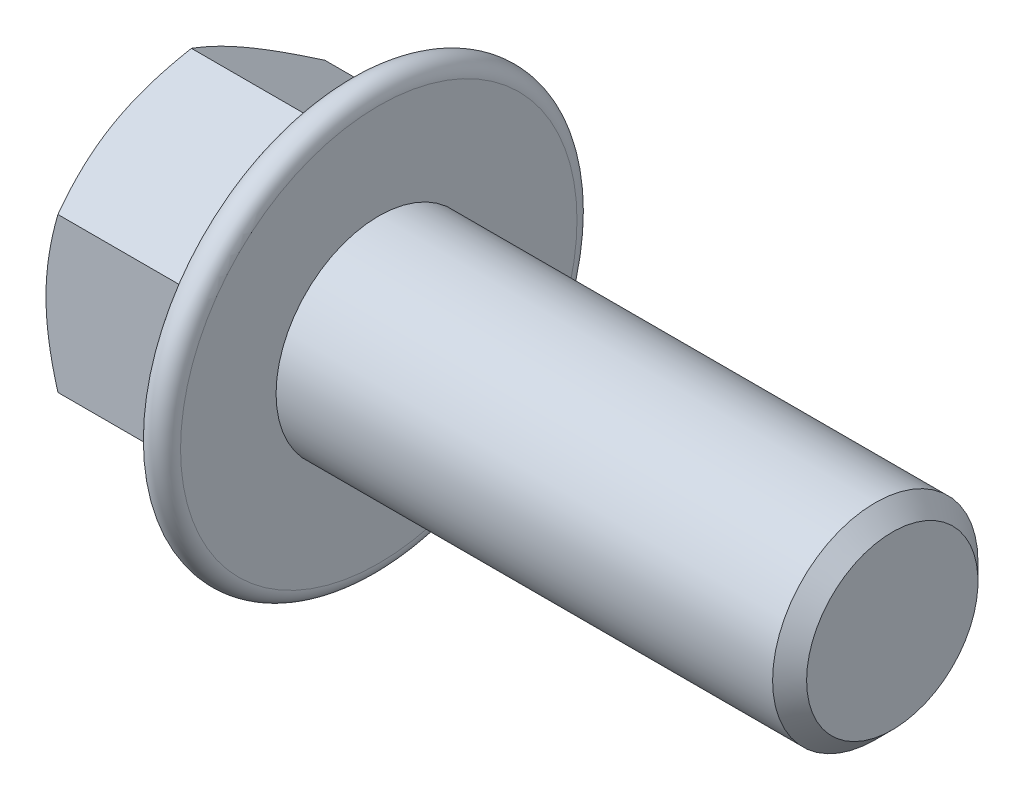
SolidWorks part; units mm, degrees
extrude "BaseHead" add sketch "Sketch1" along normal blind 9.7
sketch "Sketch1" plane through (0, 0, 0) normal (1, 0, 0) x (0, 0, -1)
  line L0 (6.5, 3.7528) -> (6.5, -3.7528)
  line L1 (-6.5, 3.7528) -> (-6.5, -3.7528)
  line L2 (6.5, -3.7528) -> (0, -7.5056)
  line L3 (0, -7.5056) -> (-6.5, -3.7528)
  line L4 (6.5, 3.7528) -> (0, 7.5056)
  line L5 (0, 7.5056) -> (-6.5, 3.7528)
  dimension "D2" = 120
  dimension "D3" = 6.5
  dimension "D4" = 6.5
  dimension "D5" = 6.5
ref_plane "Plane1" through (0, 0, 0) normal (0, 0, 1) x (1, 0, 0)
ref_plane "Plane2" through (0, 0, 0) normal (0, 1, 0) x (1, 0, 0)
ref_plane "Plane3" through (0, 0, 0) normal (1, 0, 0) x (0, 0, -1)
sketch "BodySke" plane through (0, 0, 0) normal (0, 0, 1) x (1, 0, 0)
  line L0 (0, 3.7528) -> (0, -3.7528) construction
  line L1 (0, 0) -> (34.7, 0)
  line L2 (0, 0) -> (0, 5)
  line L3 (0, 5) -> (33.872, 5)
  line L4 (34.7, 0) -> (34.7, 4.172)
  line L5 (9.7, 7.5056) -> (9.7, 3.7528) construction
  line L6 (34.7, 4.172) -> (33.872, 5)
  line L7 (0, 0) -> (96.52, 0) construction
  line L8 (34.7, -4.172) -> (33.872, -5) construction
  line L9 (0, -5) -> (33.872, -5) construction
  line L10 (11.2, 15.24) -> (11.2, -1.27) construction
  line L11 (9.7, 15.24) -> (9.7, -1.27) construction
  line L12 (9.7, 3.7528) -> (9.7, -3.7528) construction
  dimension "Diameter" = 10
revolve "BaseBody" add sketch "BodySke"
cosmetic thread "ThreadCosmetic" [suppressed]
fillet "HeadFillet" [suppressed] radius 0.4
sketch "Sketch3" plane through (0, 0, 0) normal (0, 0, 1) x (1, 0, 0)
  line L0 (0, 6.5) -> (3.4673, 12.5056)
  line L1 (0, 7.5056) -> (0, 3.7528) construction
  line L2 (3.4673, 12.5056) -> (3.4673, 17.5056)
  line L3 (3.4673, 17.5056) -> (-10, 17.5056)
  line L4 (-10, 17.5056) -> (-10, 6.5)
  line L5 (-10, 6.5) -> (0, 6.5)
  line L6 (0, 0) -> (99.06, 0) construction
  line L7 (9.7, 7.5056) -> (0, 7.5056) construction
  dimension "D1" = 6.5
  dimension "D2" = 5
  dimension "D3" = 10
  dimension "D4" = 5
  dimension "Head_ch_ang" = 30
revolve "HeadChamfer" cut sketch "Sketch3" angle 360 about L6
sketch "Sketch4" plane through (0, 0, 0) normal (0, 0, 1) x (1, 0, 0)
  line L0 (4.6396, 0) -> (8.2452, 9.9065)
  line L1 (9.7, 7.5056) -> (9.7, 3.7528) construction
  line L2 (8.2, 34.3444) -> (8.2, 16.9779) construction
  line L3 (9.7, 0) -> (9.7, 9.65)
  line L4 (8.3021, 10.4) -> (20.1618, 10.4) construction
  line L5 (0, 0) -> (95.25, 0) construction
  line L6 (0, 0) -> (96.52, 0) construction
  line L7 (4.6396, 0) -> (9.7, 0)
  line L8 (8.3021, -10.4) -> (20.1618, -10.4) construction
  arc A0 (9.7, 9.65) -> (8.2452, 9.9065) centre (8.95, 9.65) ccw
  dimension "D1" = 20
  dimension "Flange_thickness" = 1.5
  dimension "Flange_dia" = 20.8
revolve "Flange" add sketch "Sketch4" angle 360 about L5
fillet "FlangeHexFillet" radius 0.2 6 edges
sketch "ThdSchSke" plane through (0, 0, 0) normal (0, 0, 1) x (1, 0, 0)
  line L0 (11.2, -4.172) -> (10.6202, -5)
  line L1 (11.2, -4.172) -> (11.7798, -5)
  line L2 (11.7798, -5) -> (11.7798, -6.25)
  line L3 (-3.175, 0) -> (5.1513, 0) construction
  line L5 (11.7798, -6.25) -> (10.6202, -6.25)
  line L6 (10.6202, -6.25) -> (10.6202, -5)
  dimension "Thread_minor" = 8.344
  dimension "Diameter" = 10
  dimension "Start" = 11.2
revolve "ThreadSchematic" [suppressed] cut sketch "ThdSchSke" angle 360 about L3
pattern_linear "ThdSchPat" [suppressed]
equation "\"D3@Sketch1\" = \"Width_flats@Sketch1\" / 2"
equation "\"D4@Sketch1\" = \"D3@Sketch1\""
equation "\"D5@Sketch1\" = \"D4@Sketch1\""
equation "\"Thread_minor@ThreadCosmetic\" = \"Minor_dia@BodySke\""
equation "\"D1@Sketch3\" = \"Width_flats@Sketch1\" / 2"
equation "\"Thread_length@ThreadCosmetic\" = ((sgn( (\"Length@BodySke\" - \"Advance@BodySke\" ) - \"Thread_nom@BodySke\" )-1)*( (\"Length@BodySke\" - \"Advance@BodySke\" ) - \"Thread_nom@BodySke\" ))/-2+ \"Thread_nom@BodySke\""
equation "\"Thread_minor@ThdSchSke\" = \"Minor_dia@BodySke\""
equation "\"Diameter@ThdSchSke\" = \"Diameter@BodySke\""
equation "\"Overcut@ThdSchSke\" = \"Diameter@BodySke\" * 1.25"
equation "\"Start@ThdSchSke\" = \"Head_ht@BaseHead\" + \"Length@BodySke\" - \"Thread_length@ThreadCosmetic\"  '---Non-countersunk---"
equation "\"Num_threads@ThdSchPat\" = int( \"Thread_length@ThreadCosmetic\" / \"Advance@BodySke\" + 0.999 )  + 1"
equation "\"Advance@ThdSchPat\" = \"Thread_length@ThreadCosmetic\" /  (\"Num_threads@ThdSchPat\" - 1) 'relax it"
equation "\"Num_threads@ThdSchPat\" = \"Num_threads@ThdSchPat\" - sgn( \"Num_threads@ThdSchPat\" - 1) '---chamfered tips only---"
